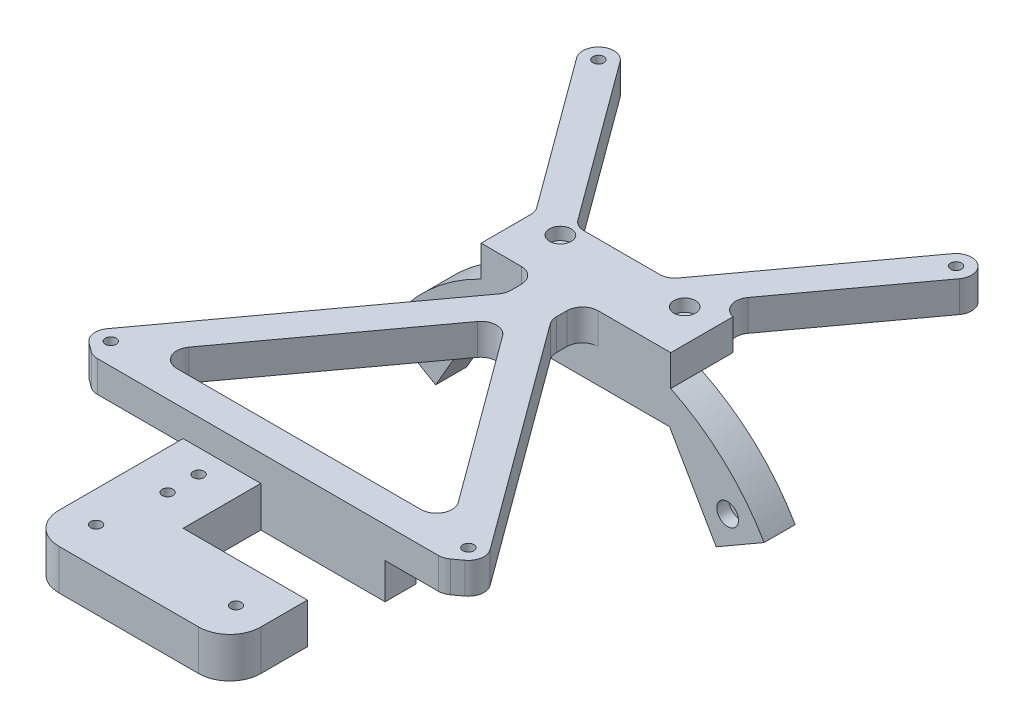
SolidWorks part; units mm, degrees
ref_plane "Plan de face" through (0, 0, 0) normal (0, 0, 1) x (1, 0, 0)
ref_plane "Plan de dessus" through (0, 0, 0) normal (0, 1, 0) x (1, 0, 0)
ref_plane "Plan de droite" through (0, 0, 0) normal (1, 0, 0) x (0, 0, -1)
sketch "Esquisse1" plane through (0, 0, 0) normal (0, 0, 1) x (1, 0, 0)
  line L0 (-30.13, 52.18) -> (30.13, 52.18)
  line L1 (30.13, 52.18) -> (45.13, 26.1992)
  line L2 (45.13, 26.1992) -> (60.5596, 35.1075)
  line L3 (-30.13, 52.18) -> (-45.13, 26.1992)
  line L4 (-45.13, 26.1992) -> (-60.5596, 35.1075)
  line L5 (-30.5123, 63) -> (30.5123, 63)
  circle A0 centre (0, 0) radius 70 construction
  arc A1 (-60.5596, 35.1075) -> (-30.5123, 63) centre (0, 0) cw
  arc A2 (60.5596, 35.1075) -> (30.5123, 63) centre (0, 0) ccw
  point P5 (0, 52.18)
  point P12 (0, 63)
  dimension "D1" = 140
  dimension "D2" = 120
  dimension "D3" = 30
  dimension "D4" = 60.26
  dimension "D5" = 61.0246
  dimension "D6" = 10.82
extrude "Boss.-Extru.1" add sketch "Esquisse1" along normal blind 10
sketch "Esquisse2" plane through (0, 63, 0) normal (0, 1, 0) x (1, 0, 0)
  line L0 (-30.5123, -10) -> (-30.5123, 0) construction
  line L1 (30.5123, -10) -> (-30.5123, -10)
  line L2 (30.5123, -10) -> (30.5123, 10)
  line L3 (30.5123, 10) -> (-30.5123, 10)
  line L4 (-30.5123, -10) -> (-30.5123, 10)
  line L5 (30.5123, 0) -> (-30.5123, 0) construction
  dimension "D1" = 10
extrude "Boss.-Extru.2" add sketch "Esquisse2" along normal blind 10
sketch "Esquisse3" plane through (0, 73, 0) normal (0, 1, 0) x (1, 0, 0)
  line L0 (30.5123, 0) -> (-30.5123, 0) construction
  line L1 (30.5123, -10) -> (30.5123, 10) construction
  line L2 (-30.5123, 10) -> (-30.5123, -10) construction
  line L3 (0, 0) -> (0, 10) construction
  line L4 (30.5123, 10) -> (-30.5123, 10) construction
  line L5 (20, 5) -> (-20, 5) construction
  circle A0 centre (20, 5) radius 1.75
  circle A1 centre (-20, 5) radius 1.75
  point P14 (0, 5)
  point P15 (0, 5)
  dimension "D1" = 3.5
  dimension "D2" = 20
extrude "Enlèv. mat.-Extru.1" cut sketch "Esquisse3" against normal up to next
sketch "Esquisse4" plane through (0, 73, 0) normal (0, 1, 0) x (1, 0, 0)
  circle A0 centre (20, 5) radius 3.5
  circle A1 centre (-20, 5) radius 3.5
  dimension "D1" = 7
extrude "Enlèv. mat.-Extru.2" cut sketch "Esquisse4" against normal blind 4
sketch "Esquisse5" plane through (0, 0, 10) normal (0, 0, 1) x (1, 0, 0)
  line L0 (-41.2992, 32.8344) -> (-56.3527, 41.5256) construction
  line L1 (-45.13, 26.1992) -> (-30.13, 52.18) construction
  line L2 (41.2992, 32.8344) -> (56.3527, 41.5256) construction
  line L3 (30.13, 52.18) -> (45.13, 26.1992) construction
  line L4 (-48.8259, 37.18) -> (48.8259, 37.18) construction
  line L5 (0, 52.18) -> (0, 37.18) construction
  line L6 (-30.13, 52.18) -> (30.13, 52.18) construction
  line L7 (-60.5596, 35.1075) -> (-45.13, 26.1992) construction
  line L8 (45.13, 26.1992) -> (60.5596, 35.1075) construction
  arc A0 (-30.5123, 63) -> (-60.5596, 35.1075) centre (0, 0) ccw construction
  arc A1 (60.5596, 35.1075) -> (30.5123, 63) centre (0, 0) ccw construction
  circle A2 centre (-48.8259, 37.18) radius 1.75
  circle A3 centre (48.8259, 37.18) radius 1.75
  dimension "D2" = 3.5
  dimension "D1" = 15
extrude "Enlèv. mat.-Extru.3" cut sketch "Esquisse5" against normal up to next
sketch "Esquisse6" plane through (0, 0, 10) normal (0, 0, 1) x (1, 0, 0)
  circle A0 centre (-48.8259, 37.18) radius 3.5
  circle A1 centre (48.8259, 37.18) radius 3.5
  dimension "D1" = 7
extrude "Enlèv. mat.-Extru.4" cut sketch "Esquisse6" against normal blind 4
sketch "Esquisse7" plane through (0, 73, 0) normal (0, 1, 0) x (1, 0, 0)
  line L0 (0, -10) -> (0, 10) construction
  line L1 (-30.5123, -10) -> (30.5123, -10) construction
  line L2 (30.5123, 10) -> (-30.5123, 10) construction
  line L3 (-62.77, -96.9) -> (52.31, 60) construction
  line L4 (52.31, -96.9) -> (-62.77, 60) construction
  line L5 (2.1076, -10) -> (2.1076, -20)
  line L6 (2.1076, -20) -> (59.2989, -97.9746)
  line L7 (59.2989, -97.9746) -> (51.2354, -103.8889)
  line L8 (51.2354, -103.8889) -> (-5.23, -26.9041)
  line L9 (-5.23, -26.9041) -> (-61.6954, -103.8889)
  line L10 (-61.6954, -103.8889) -> (-69.7589, -97.9746)
  line L11 (-69.7589, -97.9746) -> (-12.5676, -20)
  line L12 (-12.5676, -20) -> (-12.5676, -10)
  line L13 (52.31, -96.9) -> (55.2672, -100.9318) construction
  line L14 (-62.77, -96.9) -> (-65.7272, -100.9318) construction
  line L15 (9.4362, 10) -> (21.8377, 10)
  line L16 (21.8377, 10) -> (59.2989, 61.0746)
  line L17 (59.2989, 61.0746) -> (51.2354, 66.9889)
  line L18 (51.2354, 66.9889) -> (9.4362, 10)
  line L19 (52.31, 60) -> (55.2672, 64.0318) construction
  line L20 (-19.8962, 10) -> (-61.6954, 66.9889)
  line L21 (-61.6954, 66.9889) -> (-69.7589, 61.0746)
  line L22 (-69.7589, 61.0746) -> (-30.5123, 7.5658)
  line L23 (-30.5123, 10) -> (-30.5123, -10) construction
  line L24 (-30.5123, 7.5658) -> (-30.5123, 10)
  line L25 (-30.5123, 10) -> (-19.8962, 10)
  line L26 (-62.77, 60) -> (-65.7272, 64.0318) construction
  line L27 (2.1076, -10) -> (-12.5676, -10)
  circle A0 centre (52.31, -96.9) radius 1.75
  circle A1 centre (-62.77, -96.9) radius 1.75
  circle A2 centre (-62.77, 60) radius 1.75
  circle A3 centre (52.31, 60) radius 1.75
  point P10 (-5.23, -18.45)
  point P11 (-5.23, -18.45)
  dimension "D5" = 3.5
  dimension "D1" = 156.9
  dimension "D2" = 115.08
  dimension "D3" = 5.23
  dimension "D4" = 5
  dimension "D6" = 10
  dimension "D7" = 10
  dimension "D8" = 50
extrude "Boss.-Extru.3" add sketch "Esquisse7" against normal up to surface (10 mm away) up to face at (20, 63, -3.25)
sketch "Esquisse8" plane through (0, 73, 0) normal (0, 1, 0) x (1, 0, 0)
  line L0 (51.2354, -103.8889) -> (43.9008, -93.8889)
  line L1 (-5.23, -26.9041) -> (51.2354, -103.8889) construction
  line L2 (43.9008, -93.8889) -> (-54.3608, -93.8889)
  line L3 (-61.6954, -103.8889) -> (-5.23, -26.9041) construction
  line L4 (-54.3608, -93.8889) -> (-61.6954, -103.8889)
  line L5 (-61.6954, -103.8889) -> (51.2354, -103.8889)
  dimension "D1" = 10
extrude "Boss.-Extru.4" add sketch "Esquisse8" against normal up to surface (10 mm away) up to face at (-5.23, 63, 54.5146)
sketch "Esquisse9" plane through (0, 63, 0) normal (0, -1, 0) x (-1, 0, 0)
  circle A0 centre (-52.31, -96.9) radius 3.5
  circle A1 centre (62.77, -96.9) radius 3.5
  circle A2 centre (62.77, 60) radius 3.5
  circle A3 centre (-52.31, 60) radius 3.5
  dimension "D1" = 7
extrude "Enlèv. mat.-Extru.5" cut sketch "Esquisse9" against normal blind 3
ref_plane "Plan1" through (0, 64.5, 0) normal (0, -1, 0) x (-1, 0, 0)
sketch "Esquisse10" plane through (0, 64.5, 0) normal (0, -1, 0) x (-1, 0, 0)
  line L0 (54.3608, -93.8889) -> (-43.9008, -93.8889) construction
  line L1 (32.5, -153.8889) -> (-32.5, -153.8889)
  line L2 (32.5, -153.8889) -> (32.5, -93.8889)
  line L3 (32.5, -93.8889) -> (-32.5, -93.8889)
  line L4 (-32.5, -153.8889) -> (-32.5, -93.8889)
  line L5 (-51.2354, -103.8889) -> (61.6954, -103.8889) construction
  point P8 (5.23, -93.8889)
  point P9 (0, -93.8889)
  dimension "D1" = 65
  dimension "D2" = 50
  dimension "D3" = 5.23
extrude "Boss.-Extru.5" add sketch "Esquisse10" along normal blind 13
sketch "Esquisse11" plane through (0, 51.5, 0) normal (0, -1, 0) x (1, 0, 0)
  line L0 (-22.5, 141.8889) -> (22.5, 141.8889) construction
  line L1 (32.5, 153.8889) -> (-32.5, 153.8889) construction
  circle A0 centre (-22.5, 141.8889) radius 1.75
  circle A1 centre (22.5, 141.8889) radius 1.75
  point P4 (0, 141.8889)
  point P7 (0, 153.8889)
  dimension "D2" = 3.5
  dimension "D1" = 45
  dimension "D3" = 12
extrude "Enlèv. mat.-Extru.6" cut sketch "Esquisse11" against normal up to next
sketch "Esquisse12" plane through (0, 51.5, 0) normal (0, -1, 0) x (1, 0, 0)
  circle A0 centre (-22.5, 141.8889) radius 3.5
  circle A1 centre (22.5, 141.8889) radius 3.5
  dimension "D1" = 7
extrude "Enlèv. mat.-Extru.7" cut sketch "Esquisse12" against normal blind 4
fillet "Congé1" radius 10 2 edges at (32.5, 58, 153.8889) (-32.5, 58, 153.8889)
fillet "Congé2" radius 5 19 edges at (-54.3608, 68, 93.8889) (43.9008, 68, 93.8889) (59.2989, 68, 97.9746) (51.2354, 68, 103.8889) (-5.23, 68, 26.9041) (9.4362, 68, -10) (-19.8962, 68, -10) (2.1076, 68, 20) (2.1076, 68, 10) (21.8377, 68, -10) (59.2989, 68, -61.0746) (51.2354, 68, -66.9889) (-61.6954, 68, -66.9889) (-69.7589, 68, -61.0746) (-30.5123, 68, -7.5658) (-12.5676, 68, 20) (-12.5676, 68, 10) (-61.6954, 68, 103.8889) (-69.7589, 68, 97.9746)
sketch "Esquisse13" plane through (0, 64.5, 0) normal (0, 1, 0) x (1, 0, 0)
  line L1 (32.5, -103.8889) -> (-7.5, -103.8889)
  line L2 (32.5, -103.8889) -> (32.5, -128.8889)
  line L3 (32.5, -128.8889) -> (-7.5, -128.8889)
  line L4 (-7.5, -103.8889) -> (-7.5, -128.8889)
  dimension "D1" = 25
  dimension "D2" = 40
extrude "Enlèv. mat.-Extru.8" cut sketch "Esquisse13" against normal up to next
sketch "Esquisse14" plane through (0, 51.5, 0) normal (0, -1, 0) x (1, 0, 0)
  line L0 (-7.5, 116.3889) -> (-32.5, 116.3889) construction
  line L1 (-7.5, 103.8889) -> (-7.5, 128.8889) construction
  line L2 (-32.5, 143.8889) -> (-32.5, 93.8889) construction
  line L3 (-20, 121.3889) -> (-20, 111.3889) construction
  circle A0 centre (-20, 121.3889) radius 1.75
  circle A1 centre (-20, 111.3889) radius 1.75
  point P11 (-20, 116.3889)
  point P12 (-20, 116.3889)
  dimension "D1" = 3.5
  dimension "D2" = 10
extrude "Enlèv. mat.-Extru.9" cut sketch "Esquisse14" against normal up to next
sketch "Esquisse15" plane through (0, 51.5, 0) normal (0, -1, 0) x (1, 0, 0)
  circle A0 centre (-20, 121.3889) radius 3.5
  circle A1 centre (-20, 111.3889) radius 3.5
  dimension "D1" = 7
extrude "Enlèv. mat.-Extru.10" cut sketch "Esquisse15" against normal offset from surface (7 mm away) 6 up to face at (-20, 64.5, 119.6389)
